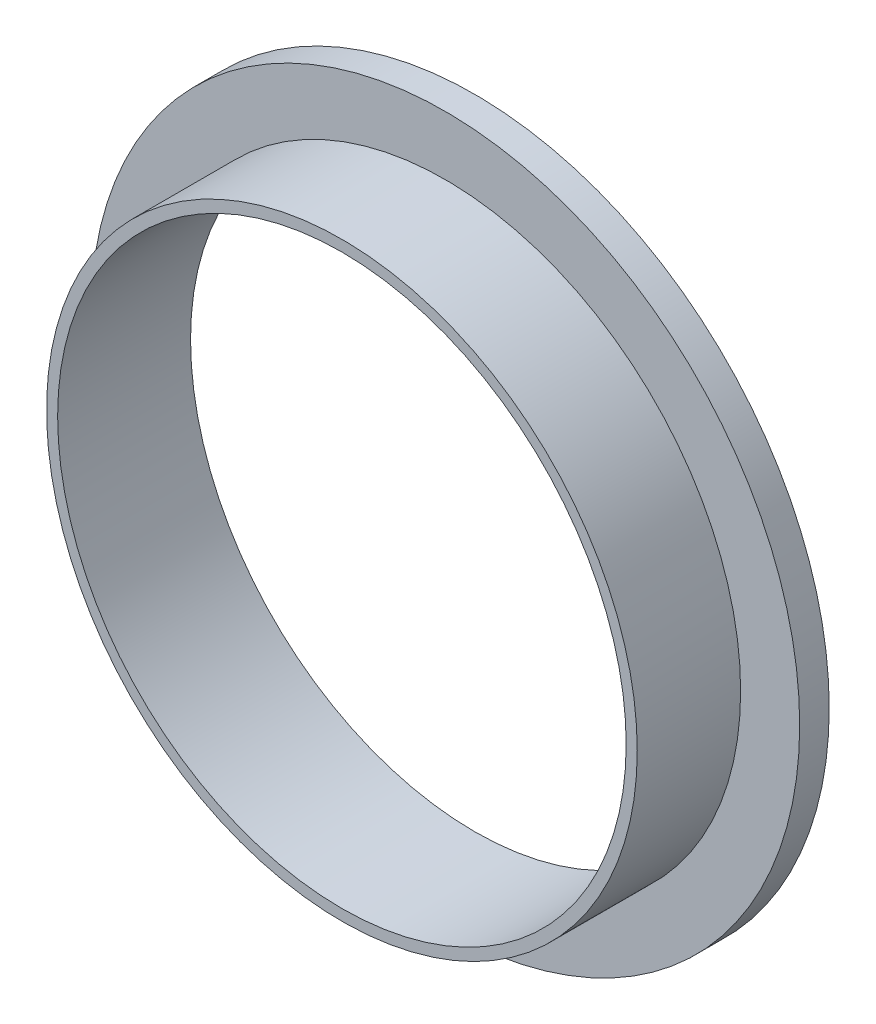
SolidWorks part; units mm, degrees
ref_plane "Plan de face" through (0, 0, 0) normal (0, 0, 1) x (1, 0, 0)
ref_plane "Plan de dessus" through (0, 0, 0) normal (0, 1, 0) x (1, 0, 0)
ref_plane "Plan de droite" through (0, 0, 0) normal (1, 0, 0) x (0, 0, -1)
sketch "Esquisse1" plane through (0, 0, 0) normal (0, 0, 1) x (1, 0, 0)
  circle A0 centre (0, 0) radius 19.25
  circle A1 centre (0, 0) radius 20
  circle A2 centre (0, 0) radius 24
  dimension "D1" = 38.5
  dimension "D2" = 40
  dimension "D3" = 48
extrude "Boss.-Extru.1" add sketch "Esquisse1" along normal blind 7 contours A1 A0 region at (-19.4343, 0, 0)
extrude "Boss.-Extru.3" add sketch "Esquisse1<4>" against normal blind 2 contours A2 A1 | A1 A0 region at (-19.4343, 0, 0) region at (-23.3212, 0, 0)
sketch "Esquisse1<4>" plane through (0, 0, 0) normal (0, 0, 1) x (1, 0, 0) same geometry as "Esquisse1"
